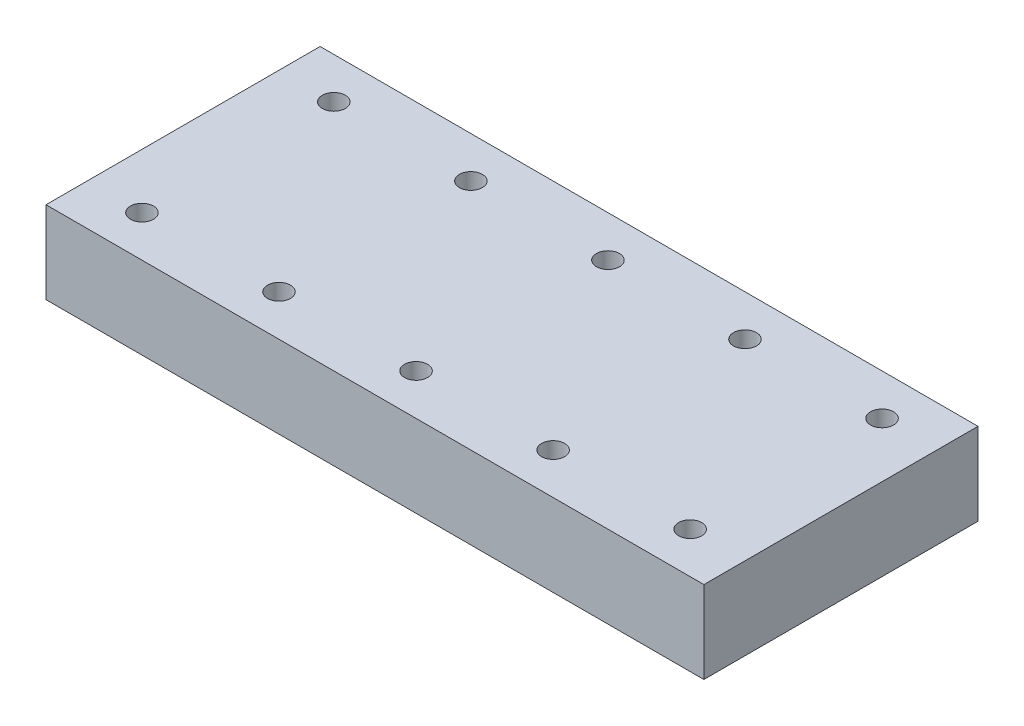
SolidWorks part; units mm, degrees
ref_plane "Front Plane" through (0, 0, 0) normal (0, 0, 1) x (1, 0, 0)
ref_plane "Top Plane" through (0, 0, 0) normal (0, 1, 0) x (1, 0, 0)
ref_plane "Right Plane" through (0, 0, 0) normal (1, 0, 0) x (0, 0, -1)
sketch "Sketch2" plane through (0, 0, 0) normal (0, 1, 0) x (1, 0, 0)
  line L0 (-46.8981, 34.5466) -> (-46.8981, -15.4534)
  line L1 (-46.8981, -15.4534) -> (73.1019, -15.4534)
  line L2 (73.1019, -15.4534) -> (73.1019, 34.5466)
  line L3 (73.1019, 34.5466) -> (-46.8981, 34.5466)
  dimension "D1" = 120
  dimension "D2" = 50
extrude "Boss-Extrude1" add sketch "Sketch2" along normal blind 15
sketch "Sketch3" plane through (0, 0, 0) normal (0, 1, 0) x (1, 0, 0)
  line L0 (74.3548, 9.5466) -> (-56.2815, 9.5466) construction
  line L1 (63.1019, 9.5466) -> (63.1019, 17.0466)
  line L2 (63.1019, 17.0466) -> (3.1019, 17.0466)
  line L3 (3.1019, 17.0466) -> (3.1019, 19.5466)
  line L4 (3.1019, 19.5466) -> (-36.8981, 19.5466)
  line L5 (-36.8981, 19.5466) -> (-36.8981, 9.5466)
  line L6 (-36.8981, 9.5466) -> (63.1019, 9.5466)
  line L7 (73.1019, -15.4534) -> (73.1019, 34.5466) construction
  line L9 (-46.8981, -15.4534) -> (73.1019, -15.4534) construction
  dimension "D1" = 60
  dimension "D2" = 40
  dimension "D3" = 10
  dimension "D4" = 25
  dimension "D5" = 10
  dimension "D6" = 7.5
revolve "Cut-Revolve8" cut sketch "Sketch3" angle 360 about L0
ref_plane "Ebene1" through (63.1019, 0, 0) normal (-1, 0, 0) x (0, 0, 1)
sketch "Skizze2" plane through (63.1019, 0, 0) normal (-1, 0, 0) x (0, 0, 1)
  line L0 (-22.101, 0) -> (5.7524, 0) construction
  line L1 (-2.0466, 0) -> (-17.0466, 0) construction
  line L2 (-9.5466, -15.2765) -> (-9.5466, 13.7911) construction
  line L3 (-3.5466, 0) -> (-2.0466, 0)
  line L4 (-2.0466, 0) -> (-17.0466, 0) construction
  line L5 (-34.5466, 15) -> (-34.5466, 0) construction
  line L6 (15.4534, 15) -> (15.4534, 0) construction
  line L7 (-4.9281, 3.83) -> (-3.7734, 4.7875)
  arc A0 (-2.0466, 0) -> (-3.7734, 4.7875) centre (-9.5466, 0) ccw
  arc A1 (-3.5466, 0) -> (-4.9281, 3.83) centre (-9.5466, 0) ccw
  dimension "D1" = 1.5
  dimension "D2" = 7.5
  dimension "D3" = 1.5
  dimension "D4" = 3.83
ref_plane "Ebene2" through (28.1019, 0, 0) normal (-1, 0, 0) x (0, 0, 1)
extrude "Aufsatz-Linear austragen3" add sketch "Skizze2" along normal blind 47.5
ref_plane "Ebene3" through (0, 0, -9.5466) normal (0, 0, 1) x (1, 0, 0)
mirror "Spiegeln1" about plane through (0, 0, -9.5466) normal (0, 0, 1) of "Aufsatz-Linear austragen3"
sketch "Skizze7" plane through (63.1019, 0, 0) normal (-1, 0, 0) x (0, 0, 1)
  line L0 (-3.5466, 0) -> (-15.5466, 0) construction
  circle A0 centre (-9.5466, 0) radius 7.5
  arc A1 (-3.7734, 4.7875) -> (-15.3198, 4.7875) centre (-9.5466, 0) ccw construction
extrude "Schnitt-Linear austragen2" cut sketch "Skizze7" against normal blind 12.5 from surface starting at plane "Ebene2"
extrude "Schnitt-Linear austragen3" cut sketch "Skizze7<2>" along normal blind 10 contours A0
sketch "Skizze7<2>" plane through (63.1019, 0, 0) normal (-1, 0, 0) x (0, 0, 1) same geometry as "Skizze7"
sketch "Skizze9" plane through (-46.8981, 0, 0) normal (-1, 0, 0) x (0, 0, 1)
  line L0 (-34.5466, 5) -> (-22.0466, 5)
  line L1 (2.9534, 5) -> (2.9534, 15)
  line L2 (15.4534, 0) -> (-34.5466, 0) construction
  line L4 (2.9534, 5) -> (15.4534, 5)
  line L5 (15.4534, 15) -> (15.4534, 0) construction
  line L6 (-34.5466, 5) -> (-34.5466, 15)
  line L7 (-34.5466, 15) -> (15.4534, 15)
  line L8 (15.4534, 15) -> (15.4534, 5)
  line L9 (2.9534, 15) -> (-22.0466, 15)
  line L10 (-22.0466, 15) -> (-22.0466, 5)
  dimension "D1" = 5
  dimension "D2" = 12.5
  dimension "D3" = 12.5
ref_plane "Ebene4" through (13.1019, 0, 0) normal (1, 0, 0) x (0, 0, -1)
ref_plane "Plane1" through (-56.8981, 0, 0) normal (-1, 0, 0) x (0, 0, 1)
sketch "Sketch4" plane through (-56.8981, 0, 0) normal (-1, 0, 0) x (0, 0, 1)
  line L0 (15.4534, 15) -> (15.4534, 0) construction
  line L1 (-34.5466, 0) -> (15.4534, 0) construction
  circle A0 centre (-9.5466, 3) radius 2
  dimension "D2" = 4
  dimension "D1" = 25
  dimension "D3" = 3
extrude "Cut-Extrude1" cut sketch "Sketch4" against normal blind 25
fillet "Fillet1" radius 1 14 edges at (53.1019, 2.0358, -3.9026) (53.1019, 2.0358, -15.1907) (28.1019, 2.0358, -15.1907) (28.1019, 2.0358, -3.9026) (46.8519, 3.83, -4.9281) (40.6019, 2.0358, -3.9026) (46.8519, 3.83, -14.1652) (40.6019, 2.0358, -15.1907) (21.8519, 3.83, -14.1652) (15.6019, 2.0358, -15.1907) (21.8519, 3.83, -4.9281) (15.6019, 2.0358, -3.9026) (3.1019, 7.5, -9.5466) (3.1019, 10, -9.5466)
sketch "Sketch5" plane through (0, 0, 0) normal (0, 1, 0) x (1, 0, 0)
  line L0 (-46.8981, 34.5466) -> (-46.8981, -15.4534) construction
  line L1 (73.1019, -15.4534) -> (73.1019, 34.5466) construction
  line L2 (73.1019, 34.5466) -> (-46.8981, 34.5466) construction
  line L3 (-46.8981, -15.4534) -> (73.1019, -15.4534) construction
  circle A0 centre (-36.8981, 27.0466) radius 2.1
  circle A1 centre (-11.8981, 27.0466) radius 2.1
  circle A2 centre (13.1019, 27.0466) radius 2.1
  circle A3 centre (38.1019, 27.0466) radius 2.1
  circle A4 centre (63.1019, 27.0466) radius 2.1
  circle A5 centre (63.1019, -7.9534) radius 2.1
  circle A6 centre (38.1019, -7.9534) radius 2.1
  circle A7 centre (13.1019, -7.9534) radius 2.1
  circle A8 centre (-11.8981, -7.9534) radius 2.1
  circle A9 centre (-36.8981, -7.9534) radius 2.1
  point P24 (-98.0812, 53.1976)
  dimension "D3" = 4.2
  dimension "D8" = 4.2
  dimension "D9" = 4.2
  dimension "D10" = 4.2
  dimension "D11" = 4.2
  dimension "D12" = 4.2
  dimension "D14" = 4.2
  dimension "D16" = 4.2
  dimension "D18" = 4.2
  dimension "D20" = 4.2
  dimension "D1" = 10
  dimension "D2" = 10
  dimension "D4" = 25
  dimension "D5" = 25
  dimension "D6" = 25
  dimension "D7" = 10
  dimension "D13" = 25
  dimension "D15" = 25
  dimension "D17" = 25
  dimension "D19" = 25
  dimension "D21" = 7.5
  dimension "D22" = 7.5
  dimension "D23" = 7.5
  dimension "D24" = 7.5
  dimension "D25" = 7.5
  dimension "D26" = 7.5
  dimension "D27" = 7.5
  dimension "D28" = 7.5
  dimension "D29" = 7.5
  dimension "D30" = 7.5
extrude "Cut-Extrude2" cut sketch "Sketch5" against normal blind 25 and the other way blind 25
